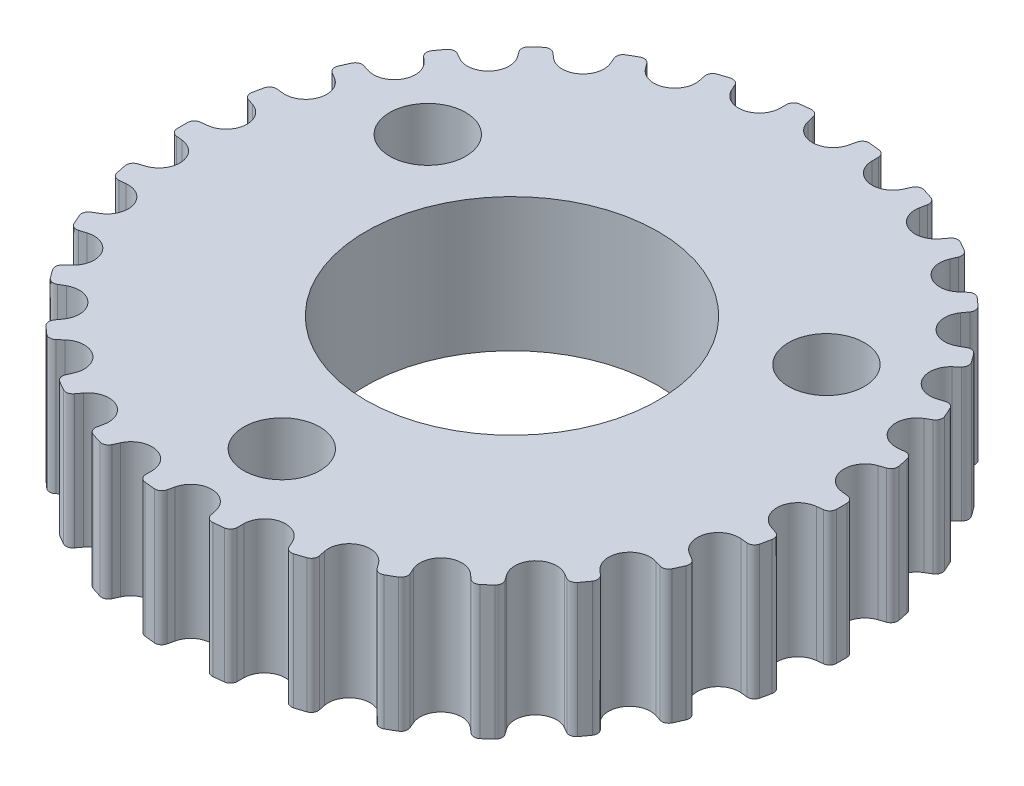
SolidWorks part; units mm, degrees
ref_plane "Front Plane" through (0, 0, 0) normal (0, 0, 1) x (1, 0, 0)
ref_plane "Top Plane" through (0, 0, 0) normal (0, 1, 0) x (1, 0, 0)
ref_plane "Right Plane" through (0, 0, 0) normal (1, 0, 0) x (0, 0, -1)
sketch "Sketch1" plane through (0, 0, 0) normal (0, 1, 0) x (1, 0, 0)
  circle A0 centre (0, 0) radius 14.3239
  dimension "D1" = 28.6479
extrude "Boss-Extrude1" add sketch "Sketch1" along normal blind 5.8
sketch "Sketch2" plane through (0, 5.8, 0) normal (0, 1, 0) x (1, 0, 0)
  line L0 (0, 0) -> (0, 14.3239) construction
  line L1 (-0.8883, 13.7564) -> (-0.95, 14.0339)
  line L2 (-2.9781, 14.0109) -> (-2.9781, 14.3239)
  line L3 (-2.9781, 14.3239) -> (2.9781, 14.3239)
  line L4 (0.8883, 13.7564) -> (0.95, 14.0339)
  line L5 (2.9781, 14.0109) -> (2.9781, 14.3239)
  circle A0 centre (0, 0) radius 14.3239 construction
  arc A1 (0.8883, 13.7564) -> (-0.8883, 13.7564) centre (0, 13.9539) cw
  arc A2 (-0.95, 14.0339) -> (-1.2694, 14.2676) centre (-1.2428, 13.9688) ccw
  arc A4 (0.95, 14.0339) -> (1.2694, 14.2676) centre (1.2428, 13.9688) cw
  arc A5 (-1.2694, 14.2676) -> (-2.9781, 14.0109) centre (0, 0) ccw
  arc A6 (1.2694, 14.2676) -> (2.9781, 14.0109) centre (0, 0) cw
  circle A8 centre (0, 0) radius 14.3239 construction
  point P11 (0, 14.3239)
  point P19 (0, 13.0439)
  dimension "D3" = 0.3
  dimension "D5" = 0.91
  dimension "D2" = 0.95
  dimension "D4" = 1.28
  dimension "D6" = 12
extrude "Cut-Extrude1" cut sketch "Sketch2" against normal through all
pattern_circular "CirPattern1" count 30 over 360 about axis through (0, 5.8, 0) along (0, -1, 0) of "Cut-Extrude1"
sketch "Sketch3" plane through (0, 0, 0) normal (0, -1, 0) x (1, 0, 0)
  circle A0 centre (0, 0) radius 6.35
  dimension "D1" = 12.7
extrude "Cut-Extrude2" cut sketch "Sketch3" against normal through all
sketch "Sketch4" plane through (0, 0, 0) normal (0, -1, 0) x (1, 0, 0)
  line L0 (0, 0) -> (0, 10) construction
  circle A0 centre (0, 10) radius 1.65
  circle A1 centre (8.6603, -5) radius 1.65
  circle A2 centre (-8.6603, -5) radius 1.65
  point P14 (0, 0)
  dimension "D1" = 3.3
  dimension "D2" = 10
  dimension "D3" = 3
extrude "Cut-Extrude3" cut sketch "Sketch4" against normal through all
sketch "Sketch5" plane through (0, 0, 0) normal (0, -1, 0) x (1, 0, 0)
  line L120 (6.3264, -12.2653) -> (6.4956, -12.4937)
  line L121 (7.5721, -11.8722) -> (7.4589, -11.6115)
  line L122 (8.7383, -10.682) -> (8.9513, -10.8702)
  line L123 (9.875, -10.0385) -> (9.7101, -9.807)
  line L124 (10.7682, -8.6318) -> (11.0157, -8.7716)
  line L125 (11.7463, -7.766) -> (11.5369, -7.5738)
  line L126 (12.3276, -6.2043) -> (12.5987, -6.2896)
  line L127 (13.1043, -5.1541) -> (12.8594, -5.0097)
  line L128 (13.3481, -3.5057) -> (13.6311, -3.5327)
  line L129 (13.8895, -2.3169) -> (13.62, -2.2266)
  line L130 (13.7853, -0.6538) -> (14.0677, -0.6215)
  line L131 (14.0677, 0.6215) -> (13.7853, 0.6538)
  line L132 (13.62, 2.2266) -> (13.8895, 2.3169)
  line L133 (13.6311, 3.5327) -> (13.3481, 3.5057)
  line L134 (12.8594, 5.0097) -> (13.1043, 5.1541)
  line L135 (12.5987, 6.2896) -> (12.3276, 6.2043)
  line L136 (11.5369, 7.5738) -> (11.7463, 7.766)
  line L137 (11.0157, 8.7716) -> (10.7682, 8.6318)
  line L138 (9.7101, 9.807) -> (9.875, 10.0385)
  line L139 (8.9513, 10.8702) -> (8.7383, 10.682)
  line L140 (7.4589, 11.6115) -> (7.5721, 11.8722)
  line L141 (6.4956, 12.4937) -> (6.3264, 12.2653)
  line L142 (4.8817, 12.9085) -> (4.9382, 13.1871)
  line L143 (3.7561, 13.5712) -> (3.638, 13.3126)
  line L144 (2.0912, 13.6414) -> (2.0886, 13.9257)
  line L145 (0.8524, 14.0556) -> (0.7907, 13.7781)
  line L146 (-0.7907, 13.7781) -> (-0.8524, 14.0556)
  line L147 (-2.0886, 13.9257) -> (-2.0912, 13.6414)
  line L148 (-3.638, 13.3126) -> (-3.7561, 13.5712)
  line L149 (-4.9382, 13.1871) -> (-4.8817, 12.9085)
  line L150 (-6.3264, 12.2653) -> (-6.4956, 12.4937)
  line L151 (-7.5721, 11.8722) -> (-7.4589, 11.6115)
  line L152 (-8.7383, 10.682) -> (-8.9513, 10.8702)
  line L153 (-9.875, 10.0385) -> (-9.7101, 9.807)
  line L154 (-10.7682, 8.6318) -> (-11.0157, 8.7716)
  line L155 (-11.7463, 7.766) -> (-11.5369, 7.5738)
  line L156 (-12.3276, 6.2043) -> (-12.5987, 6.2896)
  line L157 (-13.1043, 5.1541) -> (-12.8594, 5.0097)
  line L158 (-13.3481, 3.5057) -> (-13.6311, 3.5327)
  line L159 (-13.8895, 2.3169) -> (-13.62, 2.2266)
  line L160 (-13.7853, 0.6538) -> (-14.0677, 0.6215)
  line L161 (-14.0677, -0.6215) -> (-13.7853, -0.6538)
  line L162 (-13.62, -2.2266) -> (-13.8895, -2.3169)
  line L163 (-13.6311, -3.5327) -> (-13.3481, -3.5057)
  line L164 (-12.8594, -5.0097) -> (-13.1043, -5.1541)
  line L165 (-12.5987, -6.2896) -> (-12.3276, -6.2043)
  line L166 (-11.5369, -7.5738) -> (-11.7463, -7.766)
  line L167 (-11.0157, -8.7716) -> (-10.7682, -8.6318)
  line L168 (-9.7101, -9.807) -> (-9.875, -10.0385)
  line L169 (-8.9513, -10.8702) -> (-8.7383, -10.682)
  line L170 (-7.4589, -11.6115) -> (-7.5721, -11.8722)
  line L171 (-6.4956, -12.4937) -> (-6.3264, -12.2653)
  line L172 (-4.8817, -12.9085) -> (-4.9382, -13.1871)
  line L173 (-3.7561, -13.5712) -> (-3.638, -13.3126)
  line L174 (-2.0912, -13.6414) -> (-2.0886, -13.9257)
  line L175 (-0.8524, -14.0556) -> (-0.7907, -13.7781)
  line L176 (0.7907, -13.7781) -> (0.8524, -14.0556)
  line L177 (2.0886, -13.9257) -> (2.0912, -13.6414)
  line L178 (3.638, -13.3126) -> (3.7561, -13.5712)
  line L179 (4.9382, -13.1871) -> (4.8817, -12.9085)
  line L180 (6.3264, -12.2653) -> (6.4956, -12.4937)
  line L181 (7.5721, -11.8722) -> (7.4589, -11.6115)
  line L182 (8.7383, -10.682) -> (8.9513, -10.8702)
  line L183 (9.875, -10.0385) -> (9.7101, -9.807)
  line L184 (10.7682, -8.6318) -> (11.0157, -8.7716)
  line L185 (11.7463, -7.766) -> (11.5369, -7.5738)
  line L186 (12.3276, -6.2043) -> (12.5987, -6.2896)
  line L187 (13.1043, -5.1541) -> (12.8594, -5.0097)
  line L188 (13.3481, -3.5057) -> (13.6311, -3.5327)
  line L189 (13.8895, -2.3169) -> (13.62, -2.2266)
  line L190 (13.7853, -0.6538) -> (14.0677, -0.6215)
  line L191 (14.0677, 0.6215) -> (13.7853, 0.6538)
  line L192 (13.62, 2.2266) -> (13.8895, 2.3169)
  line L193 (13.6311, 3.5327) -> (13.3481, 3.5057)
  line L194 (12.8594, 5.0097) -> (13.1043, 5.1541)
  line L195 (12.5987, 6.2896) -> (12.3276, 6.2043)
  line L196 (11.5369, 7.5738) -> (11.7463, 7.766)
  line L197 (11.0157, 8.7716) -> (10.7682, 8.6318)
  line L198 (9.7101, 9.807) -> (9.875, 10.0385)
  line L199 (8.9513, 10.8702) -> (8.7383, 10.682)
  line L200 (7.4589, 11.6115) -> (7.5721, 11.8722)
  line L201 (6.4956, 12.4937) -> (6.3264, 12.2653)
  line L202 (4.8817, 12.9085) -> (4.9382, 13.1871)
  line L203 (3.7561, 13.5712) -> (3.638, 13.3126)
  line L204 (2.0912, 13.6414) -> (2.0886, 13.9257)
  line L205 (0.8524, 14.0556) -> (0.7907, 13.7781)
  line L206 (-0.7907, 13.7781) -> (-0.8524, 14.0556)
  line L207 (-2.0886, 13.9257) -> (-2.0912, 13.6414)
  line L208 (-3.638, 13.3126) -> (-3.7561, 13.5712)
  line L209 (-4.9382, 13.1871) -> (-4.8817, 12.9085)
  line L210 (-6.3264, 12.2653) -> (-6.4956, 12.4937)
  line L211 (-7.5721, 11.8722) -> (-7.4589, 11.6115)
  line L212 (-8.7383, 10.682) -> (-8.9513, 10.8702)
  line L213 (-9.875, 10.0385) -> (-9.7101, 9.807)
  line L214 (-10.7682, 8.6318) -> (-11.0157, 8.7716)
  line L215 (-11.7463, 7.766) -> (-11.5369, 7.5738)
  line L216 (-12.3276, 6.2043) -> (-12.5987, 6.2896)
  line L217 (-13.1043, 5.1541) -> (-12.8594, 5.0097)
  line L218 (-13.3481, 3.5057) -> (-13.6311, 3.5327)
  line L219 (-13.8895, 2.3169) -> (-13.62, 2.2266)
  line L220 (-13.7853, 0.6538) -> (-14.0677, 0.6215)
  line L221 (-14.0677, -0.6215) -> (-13.7853, -0.6538)
  line L222 (-13.62, -2.2266) -> (-13.8895, -2.3169)
  line L223 (-13.6311, -3.5327) -> (-13.3481, -3.5057)
  line L224 (-12.8594, -5.0097) -> (-13.1043, -5.1541)
  line L225 (-12.5987, -6.2896) -> (-12.3276, -6.2043)
  line L226 (-11.5369, -7.5738) -> (-11.7463, -7.766)
  line L227 (-11.0157, -8.7716) -> (-10.7682, -8.6318)
  line L228 (-9.7101, -9.807) -> (-9.875, -10.0385)
  line L229 (-8.9513, -10.8702) -> (-8.7383, -10.682)
  line L230 (-7.4589, -11.6115) -> (-7.5721, -11.8722)
  line L231 (-6.4956, -12.4937) -> (-6.3264, -12.2653)
  line L232 (-4.8817, -12.9085) -> (-4.9382, -13.1871)
  line L233 (-3.7561, -13.5712) -> (-3.638, -13.3126)
  line L234 (-2.0912, -13.6414) -> (-2.0886, -13.9257)
  line L235 (-0.8524, -14.0556) -> (-0.7907, -13.7781)
  line L236 (0.7907, -13.7781) -> (0.8524, -14.0556)
  line L237 (2.0886, -13.9257) -> (2.0912, -13.6414)
  line L238 (3.638, -13.3126) -> (3.7561, -13.5712)
  line L239 (4.9382, -13.1871) -> (4.8817, -12.9085)
  circle A120 centre (0, 0) radius 13.0439
  arc A121 (-0.8883, 13.7564) -> (0.8883, 13.7564) centre (0, 13.9539) ccw construction
  arc A240 (6.4956, -12.4937) -> (7.0114, -12.6052) centre (6.817, -12.2556) ccw
  arc A241 (7.0114, -12.6052) -> (7.4107, -12.3747) centre (0, 0) ccw
  arc A242 (7.4107, -12.3747) -> (7.5721, -11.8722) centre (7.2051, -12.0315) ccw
  arc A243 (8.7383, -10.682) -> (7.4589, -11.6115) centre (8.2019, -11.289) ccw
  arc A244 (8.9513, -10.8702) -> (9.479, -10.8719) centre (9.2161, -10.5704) ccw
  arc A245 (9.479, -10.8719) -> (9.8216, -10.5635) centre (0, 0) ccw
  arc A246 (9.8216, -10.5635) -> (9.875, -10.0385) centre (9.5492, -10.2705) ccw
  arc A247 (10.7682, -8.6318) -> (9.7101, -9.807) centre (10.3698, -9.337) ccw
  arc A248 (11.0157, -8.7716) -> (11.5323, -8.6636) centre (11.2124, -8.4233) ccw
  arc A249 (11.5323, -8.6636) -> (11.8032, -8.2906) centre (0, 0) ccw
  arc A250 (11.8032, -8.2906) -> (11.7463, -7.766) centre (11.4759, -8.0607) ccw
  arc A251 (12.3276, -6.2043) -> (11.5369, -7.5738) centre (12.0845, -6.977) ccw
  arc A252 (12.5987, -6.2896) -> (13.0815, -6.0766) centre (12.7187, -5.908) ccw
  arc A253 (13.0815, -6.0766) -> (13.269, -5.6554) centre (0, 0) ccw
  arc A254 (13.269, -5.6554) -> (13.1043, -5.1541) centre (12.901, -5.4986) ccw
  arc A255 (13.3481, -3.5057) -> (12.8594, -5.0097) centre (13.271, -4.312) ccw
  arc A256 (13.6311, -3.5327) -> (14.059, -3.224) centre (13.6691, -3.1346) ccw
  arc A257 (14.059, -3.224) -> (14.1549, -2.7731) centre (0, 0) ccw
  arc A258 (14.1549, -2.7731) -> (13.8895, -2.3169) centre (13.7623, -2.6962) ccw
  arc A259 (13.7853, -0.6538) -> (13.62, -2.2266) centre (13.8775, -1.4586) ccw
  arc A260 (14.0677, -0.6215) -> (14.4221, -0.2305) centre (14.0222, -0.2241) ccw
  arc A261 (14.4221, -0.2305) -> (14.4221, 0.2305) centre (0, 0) ccw
  arc A262 (14.4221, 0.2305) -> (14.0677, 0.6215) centre (14.0222, 0.2241) ccw
  arc A263 (13.62, 2.2266) -> (13.7853, 0.6538) centre (13.8775, 1.4586) ccw
  arc A264 (13.8895, 2.3169) -> (14.1549, 2.7731) centre (13.7623, 2.6962) ccw
  arc A265 (14.1549, 2.7731) -> (14.059, 3.224) centre (0, 0) ccw
  arc A266 (14.059, 3.224) -> (13.6311, 3.5327) centre (13.6691, 3.1346) ccw
  arc A267 (12.8594, 5.0097) -> (13.3481, 3.5057) centre (13.271, 4.312) ccw
  arc A268 (13.1043, 5.1541) -> (13.269, 5.6554) centre (12.901, 5.4986) ccw
  arc A269 (13.269, 5.6554) -> (13.0815, 6.0766) centre (0, 0) ccw
  arc A270 (13.0815, 6.0766) -> (12.5987, 6.2896) centre (12.7187, 5.908) ccw
  arc A271 (11.5369, 7.5738) -> (12.3276, 6.2043) centre (12.0845, 6.977) ccw
  arc A272 (11.7463, 7.766) -> (11.8032, 8.2906) centre (11.4759, 8.0607) ccw
  arc A273 (11.8032, 8.2906) -> (11.5323, 8.6636) centre (0, 0) ccw
  arc A274 (11.5323, 8.6636) -> (11.0157, 8.7716) centre (11.2124, 8.4233) ccw
  arc A275 (9.7101, 9.807) -> (10.7682, 8.6318) centre (10.3698, 9.337) ccw
  arc A276 (9.875, 10.0385) -> (9.8216, 10.5635) centre (9.5492, 10.2705) ccw
  arc A277 (9.8216, 10.5635) -> (9.479, 10.8719) centre (0, 0) ccw
  arc A278 (9.479, 10.8719) -> (8.9513, 10.8702) centre (9.2161, 10.5704) ccw
  arc A279 (7.4589, 11.6115) -> (8.7383, 10.682) centre (8.2019, 11.289) ccw
  arc A280 (7.5721, 11.8722) -> (7.4107, 12.3747) centre (7.2051, 12.0315) ccw
  arc A281 (7.4107, 12.3747) -> (7.0114, 12.6052) centre (0, 0) ccw
  arc A282 (7.0114, 12.6052) -> (6.4956, 12.4937) centre (6.817, 12.2556) ccw
  arc A283 (4.8817, 12.9085) -> (6.3264, 12.2653) centre (5.6756, 12.7476) ccw
  arc A284 (4.9382, 13.1871) -> (4.6759, 13.645) centre (4.5462, 13.2666) ccw
  arc A285 (4.6759, 13.645) -> (4.2375, 13.7875) centre (0, 0) ccw
  arc A286 (4.2375, 13.7875) -> (3.7561, 13.5712) centre (4.12, 13.4051) ccw
  arc A287 (2.0912, 13.6414) -> (3.638, 13.3126) centre (2.9012, 13.649) ccw
  arc A288 (2.0886, 13.9257) -> (1.7367, 14.319) centre (1.6886, 13.9219) ccw
  arc A289 (1.7367, 14.319) -> (1.2783, 14.3672) centre (0, 0) ccw
  arc A290 (1.2783, 14.3672) -> (0.8524, 14.0556) centre (1.2428, 13.9688) ccw
  arc A291 (-0.7907, 13.7781) -> (0.7907, 13.7781) centre (0, 13.9539) ccw
  arc A292 (-0.8524, 14.0556) -> (-1.2783, 14.3672) centre (-1.2428, 13.9688) ccw
  arc A293 (-1.2783, 14.3672) -> (-1.7367, 14.319) centre (0, 0) ccw
  arc A294 (-1.7367, 14.319) -> (-2.0886, 13.9257) centre (-1.6886, 13.9219) ccw
  arc A295 (-3.638, 13.3126) -> (-2.0912, 13.6414) centre (-2.9012, 13.649) ccw
  arc A296 (-3.7561, 13.5712) -> (-4.2375, 13.7875) centre (-4.12, 13.4051) ccw
  arc A297 (-4.2375, 13.7875) -> (-4.6759, 13.645) centre (0, 0) ccw
  arc A298 (-4.6759, 13.645) -> (-4.9382, 13.1871) centre (-4.5462, 13.2666) ccw
  arc A299 (-6.3264, 12.2653) -> (-4.8817, 12.9085) centre (-5.6756, 12.7476) ccw
  arc A300 (-6.4956, 12.4937) -> (-7.0114, 12.6052) centre (-6.817, 12.2556) ccw
  arc A301 (-7.0114, 12.6052) -> (-7.4107, 12.3747) centre (0, 0) ccw
  arc A302 (-7.4107, 12.3747) -> (-7.5721, 11.8722) centre (-7.2051, 12.0315) ccw
  arc A303 (-8.7383, 10.682) -> (-7.4589, 11.6115) centre (-8.2019, 11.289) ccw
  arc A304 (-8.9513, 10.8702) -> (-9.479, 10.8719) centre (-9.2161, 10.5704) ccw
  arc A305 (-9.479, 10.8719) -> (-9.8216, 10.5635) centre (0, 0) ccw
  arc A306 (-9.8216, 10.5635) -> (-9.875, 10.0385) centre (-9.5492, 10.2705) ccw
  arc A307 (-10.7682, 8.6318) -> (-9.7101, 9.807) centre (-10.3698, 9.337) ccw
  arc A308 (-11.0157, 8.7716) -> (-11.5323, 8.6636) centre (-11.2124, 8.4233) ccw
  arc A309 (-11.5323, 8.6636) -> (-11.8032, 8.2906) centre (0, 0) ccw
  arc A310 (-11.8032, 8.2906) -> (-11.7463, 7.766) centre (-11.4759, 8.0607) ccw
  arc A311 (-12.3276, 6.2043) -> (-11.5369, 7.5738) centre (-12.0845, 6.977) ccw
  arc A312 (-12.5987, 6.2896) -> (-13.0815, 6.0766) centre (-12.7187, 5.908) ccw
  arc A313 (-13.0815, 6.0766) -> (-13.269, 5.6554) centre (0, 0) ccw
  arc A314 (-13.269, 5.6554) -> (-13.1043, 5.1541) centre (-12.901, 5.4986) ccw
  arc A315 (-13.3481, 3.5057) -> (-12.8594, 5.0097) centre (-13.271, 4.312) ccw
  arc A316 (-13.6311, 3.5327) -> (-14.059, 3.224) centre (-13.6691, 3.1346) ccw
  arc A317 (-14.059, 3.224) -> (-14.1549, 2.7731) centre (0, 0) ccw
  arc A318 (-14.1549, 2.7731) -> (-13.8895, 2.3169) centre (-13.7623, 2.6962) ccw
  arc A319 (-13.7853, 0.6538) -> (-13.62, 2.2266) centre (-13.8775, 1.4586) ccw
  arc A320 (-14.0677, 0.6215) -> (-14.4221, 0.2305) centre (-14.0222, 0.2241) ccw
  arc A321 (-14.4221, 0.2305) -> (-14.4221, -0.2305) centre (0, 0) ccw
  arc A322 (-14.4221, -0.2305) -> (-14.0677, -0.6215) centre (-14.0222, -0.2241) ccw
  arc A323 (-13.62, -2.2266) -> (-13.7853, -0.6538) centre (-13.8775, -1.4586) ccw
  arc A324 (-13.8895, -2.3169) -> (-14.1549, -2.7731) centre (-13.7623, -2.6962) ccw
  arc A325 (-14.1549, -2.7731) -> (-14.059, -3.224) centre (0, 0) ccw
  arc A326 (-14.059, -3.224) -> (-13.6311, -3.5327) centre (-13.6691, -3.1346) ccw
  arc A327 (-12.8594, -5.0097) -> (-13.3481, -3.5057) centre (-13.271, -4.312) ccw
  arc A328 (-13.1043, -5.1541) -> (-13.269, -5.6554) centre (-12.901, -5.4986) ccw
  arc A329 (-13.269, -5.6554) -> (-13.0815, -6.0766) centre (0, 0) ccw
  arc A330 (-13.0815, -6.0766) -> (-12.5987, -6.2896) centre (-12.7187, -5.908) ccw
  arc A331 (-11.5369, -7.5738) -> (-12.3276, -6.2043) centre (-12.0845, -6.977) ccw
  arc A332 (-11.7463, -7.766) -> (-11.8032, -8.2906) centre (-11.4759, -8.0607) ccw
  arc A333 (-11.8032, -8.2906) -> (-11.5323, -8.6636) centre (0, 0) ccw
  arc A334 (-11.5323, -8.6636) -> (-11.0157, -8.7716) centre (-11.2124, -8.4233) ccw
  arc A335 (-9.7101, -9.807) -> (-10.7682, -8.6318) centre (-10.3698, -9.337) ccw
  arc A336 (-9.875, -10.0385) -> (-9.8216, -10.5635) centre (-9.5492, -10.2705) ccw
  arc A337 (-9.8216, -10.5635) -> (-9.479, -10.8719) centre (0, 0) ccw
  arc A338 (-9.479, -10.8719) -> (-8.9513, -10.8702) centre (-9.2161, -10.5704) ccw
  arc A339 (-7.4589, -11.6115) -> (-8.7383, -10.682) centre (-8.2019, -11.289) ccw
  arc A340 (-7.5721, -11.8722) -> (-7.4107, -12.3747) centre (-7.2051, -12.0315) ccw
  arc A341 (-7.4107, -12.3747) -> (-7.0114, -12.6052) centre (0, 0) ccw
  arc A342 (-7.0114, -12.6052) -> (-6.4956, -12.4937) centre (-6.817, -12.2556) ccw
  arc A343 (-4.8817, -12.9085) -> (-6.3264, -12.2653) centre (-5.6756, -12.7476) ccw
  arc A344 (-4.9382, -13.1871) -> (-4.6759, -13.645) centre (-4.5462, -13.2666) ccw
  arc A345 (-4.6759, -13.645) -> (-4.2375, -13.7875) centre (0, 0) ccw
  arc A346 (-4.2375, -13.7875) -> (-3.7561, -13.5712) centre (-4.12, -13.4051) ccw
  arc A347 (-2.0912, -13.6414) -> (-3.638, -13.3126) centre (-2.9012, -13.649) ccw
  arc A348 (-2.0886, -13.9257) -> (-1.7367, -14.319) centre (-1.6886, -13.9219) ccw
  arc A349 (-1.7367, -14.319) -> (-1.2783, -14.3672) centre (0, 0) ccw
  arc A350 (-1.2783, -14.3672) -> (-0.8524, -14.0556) centre (-1.2428, -13.9688) ccw
  arc A351 (0.7907, -13.7781) -> (-0.7907, -13.7781) centre (0, -13.9539) ccw
  arc A352 (0.8524, -14.0556) -> (1.2783, -14.3672) centre (1.2428, -13.9688) ccw
  arc A353 (1.2783, -14.3672) -> (1.7367, -14.319) centre (0, 0) ccw
  arc A354 (1.7367, -14.319) -> (2.0886, -13.9257) centre (1.6886, -13.9219) ccw
  arc A355 (3.638, -13.3126) -> (2.0912, -13.6414) centre (2.9012, -13.649) ccw
  arc A356 (3.7561, -13.5712) -> (4.2375, -13.7875) centre (4.12, -13.4051) ccw
  arc A357 (4.2375, -13.7875) -> (4.6759, -13.645) centre (0, 0) ccw
  arc A358 (4.6759, -13.645) -> (4.9382, -13.1871) centre (4.5462, -13.2666) ccw
  arc A359 (6.3264, -12.2653) -> (4.8817, -12.9085) centre (5.6756, -12.7476) ccw
  arc A360 (6.4956, -12.4937) -> (7.0114, -12.6052) centre (6.817, -12.2556) ccw
  arc A361 (7.0114, -12.6052) -> (7.4107, -12.3747) centre (0, 0) ccw
  arc A362 (7.4107, -12.3747) -> (7.5721, -11.8722) centre (7.2051, -12.0315) ccw
  arc A363 (8.7383, -10.682) -> (7.4589, -11.6115) centre (8.2019, -11.289) ccw
  arc A364 (8.9513, -10.8702) -> (9.479, -10.8719) centre (9.2161, -10.5704) ccw
  arc A365 (9.479, -10.8719) -> (9.8216, -10.5635) centre (0, 0) ccw
  arc A366 (9.8216, -10.5635) -> (9.875, -10.0385) centre (9.5492, -10.2705) ccw
  arc A367 (10.7682, -8.6318) -> (9.7101, -9.807) centre (10.3698, -9.337) ccw
  arc A368 (11.0157, -8.7716) -> (11.5323, -8.6636) centre (11.2124, -8.4233) ccw
  arc A369 (11.5323, -8.6636) -> (11.8032, -8.2906) centre (0, 0) ccw
  arc A370 (11.8032, -8.2906) -> (11.7463, -7.766) centre (11.4759, -8.0607) ccw
  arc A371 (12.3276, -6.2043) -> (11.5369, -7.5738) centre (12.0845, -6.977) ccw
  arc A372 (12.5987, -6.2896) -> (13.0815, -6.0766) centre (12.7187, -5.908) ccw
  arc A373 (13.0815, -6.0766) -> (13.269, -5.6554) centre (0, 0) ccw
  arc A374 (13.269, -5.6554) -> (13.1043, -5.1541) centre (12.901, -5.4986) ccw
  arc A375 (13.3481, -3.5057) -> (12.8594, -5.0097) centre (13.271, -4.312) ccw
  arc A376 (13.6311, -3.5327) -> (14.059, -3.224) centre (13.6691, -3.1346) ccw
  arc A377 (14.059, -3.224) -> (14.1549, -2.7731) centre (0, 0) ccw
  arc A378 (14.1549, -2.7731) -> (13.8895, -2.3169) centre (13.7623, -2.6962) ccw
  arc A379 (13.7853, -0.6538) -> (13.62, -2.2266) centre (13.8775, -1.4586) ccw
  arc A380 (14.0677, -0.6215) -> (14.4221, -0.2305) centre (14.0222, -0.2241) ccw
  arc A381 (14.4221, -0.2305) -> (14.4221, 0.2305) centre (0, 0) ccw
  arc A382 (14.4221, 0.2305) -> (14.0677, 0.6215) centre (14.0222, 0.2241) ccw
  arc A383 (13.62, 2.2266) -> (13.7853, 0.6538) centre (13.8775, 1.4586) ccw
  arc A384 (13.8895, 2.3169) -> (14.1549, 2.7731) centre (13.7623, 2.6962) ccw
  arc A385 (14.1549, 2.7731) -> (14.059, 3.224) centre (0, 0) ccw
  arc A386 (14.059, 3.224) -> (13.6311, 3.5327) centre (13.6691, 3.1346) ccw
  arc A387 (12.8594, 5.0097) -> (13.3481, 3.5057) centre (13.271, 4.312) ccw
  arc A388 (13.1043, 5.1541) -> (13.269, 5.6554) centre (12.901, 5.4986) ccw
  arc A389 (13.269, 5.6554) -> (13.0815, 6.0766) centre (0, 0) ccw
  arc A390 (13.0815, 6.0766) -> (12.5987, 6.2896) centre (12.7187, 5.908) ccw
  arc A391 (11.5369, 7.5738) -> (12.3276, 6.2043) centre (12.0845, 6.977) ccw
  arc A392 (11.7463, 7.766) -> (11.8032, 8.2906) centre (11.4759, 8.0607) ccw
  arc A393 (11.8032, 8.2906) -> (11.5323, 8.6636) centre (0, 0) ccw
  arc A394 (11.5323, 8.6636) -> (11.0157, 8.7716) centre (11.2124, 8.4233) ccw
  arc A395 (9.7101, 9.807) -> (10.7682, 8.6318) centre (10.3698, 9.337) ccw
  arc A396 (9.875, 10.0385) -> (9.8216, 10.5635) centre (9.5492, 10.2705) ccw
  arc A397 (9.8216, 10.5635) -> (9.479, 10.8719) centre (0, 0) ccw
  arc A398 (9.479, 10.8719) -> (8.9513, 10.8702) centre (9.2161, 10.5704) ccw
  arc A399 (7.4589, 11.6115) -> (8.7383, 10.682) centre (8.2019, 11.289) ccw
  arc A400 (7.5721, 11.8722) -> (7.4107, 12.3747) centre (7.2051, 12.0315) ccw
  arc A401 (7.4107, 12.3747) -> (7.0114, 12.6052) centre (0, 0) ccw
  arc A402 (7.0114, 12.6052) -> (6.4956, 12.4937) centre (6.817, 12.2556) ccw
  arc A403 (4.8817, 12.9085) -> (6.3264, 12.2653) centre (5.6756, 12.7476) ccw
  arc A404 (4.9382, 13.1871) -> (4.6759, 13.645) centre (4.5462, 13.2666) ccw
  arc A405 (4.6759, 13.645) -> (4.2375, 13.7875) centre (0, 0) ccw
  arc A406 (4.2375, 13.7875) -> (3.7561, 13.5712) centre (4.12, 13.4051) ccw
  arc A407 (2.0912, 13.6414) -> (3.638, 13.3126) centre (2.9012, 13.649) ccw
  arc A408 (2.0886, 13.9257) -> (1.7367, 14.319) centre (1.6886, 13.9219) ccw
  arc A409 (1.7367, 14.319) -> (1.2783, 14.3672) centre (0, 0) ccw
  arc A410 (1.2783, 14.3672) -> (0.8524, 14.0556) centre (1.2428, 13.9688) ccw
  arc A411 (-0.7907, 13.7781) -> (0.7907, 13.7781) centre (0, 13.9539) ccw
  arc A412 (-0.8524, 14.0556) -> (-1.2783, 14.3672) centre (-1.2428, 13.9688) ccw
  arc A413 (-1.2783, 14.3672) -> (-1.7367, 14.319) centre (0, 0) ccw
  arc A414 (-1.7367, 14.319) -> (-2.0886, 13.9257) centre (-1.6886, 13.9219) ccw
  arc A415 (-3.638, 13.3126) -> (-2.0912, 13.6414) centre (-2.9012, 13.649) ccw
  arc A416 (-3.7561, 13.5712) -> (-4.2375, 13.7875) centre (-4.12, 13.4051) ccw
  arc A417 (-4.2375, 13.7875) -> (-4.6759, 13.645) centre (0, 0) ccw
  arc A418 (-4.6759, 13.645) -> (-4.9382, 13.1871) centre (-4.5462, 13.2666) ccw
  arc A419 (-6.3264, 12.2653) -> (-4.8817, 12.9085) centre (-5.6756, 12.7476) ccw
  arc A420 (-6.4956, 12.4937) -> (-7.0114, 12.6052) centre (-6.817, 12.2556) ccw
  arc A421 (-7.0114, 12.6052) -> (-7.4107, 12.3747) centre (0, 0) ccw
  arc A422 (-7.4107, 12.3747) -> (-7.5721, 11.8722) centre (-7.2051, 12.0315) ccw
  arc A423 (-8.7383, 10.682) -> (-7.4589, 11.6115) centre (-8.2019, 11.289) ccw
  arc A424 (-8.9513, 10.8702) -> (-9.479, 10.8719) centre (-9.2161, 10.5704) ccw
  arc A425 (-9.479, 10.8719) -> (-9.8216, 10.5635) centre (0, 0) ccw
  arc A426 (-9.8216, 10.5635) -> (-9.875, 10.0385) centre (-9.5492, 10.2705) ccw
  arc A427 (-10.7682, 8.6318) -> (-9.7101, 9.807) centre (-10.3698, 9.337) ccw
  arc A428 (-11.0157, 8.7716) -> (-11.5323, 8.6636) centre (-11.2124, 8.4233) ccw
  arc A429 (-11.5323, 8.6636) -> (-11.8032, 8.2906) centre (0, 0) ccw
  arc A430 (-11.8032, 8.2906) -> (-11.7463, 7.766) centre (-11.4759, 8.0607) ccw
  arc A431 (-12.3276, 6.2043) -> (-11.5369, 7.5738) centre (-12.0845, 6.977) ccw
  arc A432 (-12.5987, 6.2896) -> (-13.0815, 6.0766) centre (-12.7187, 5.908) ccw
  arc A433 (-13.0815, 6.0766) -> (-13.269, 5.6554) centre (0, 0) ccw
  arc A434 (-13.269, 5.6554) -> (-13.1043, 5.1541) centre (-12.901, 5.4986) ccw
  arc A435 (-13.3481, 3.5057) -> (-12.8594, 5.0097) centre (-13.271, 4.312) ccw
  arc A436 (-13.6311, 3.5327) -> (-14.059, 3.224) centre (-13.6691, 3.1346) ccw
  arc A437 (-14.059, 3.224) -> (-14.1549, 2.7731) centre (0, 0) ccw
  arc A438 (-14.1549, 2.7731) -> (-13.8895, 2.3169) centre (-13.7623, 2.6962) ccw
  arc A439 (-13.7853, 0.6538) -> (-13.62, 2.2266) centre (-13.8775, 1.4586) ccw
  arc A440 (-14.0677, 0.6215) -> (-14.4221, 0.2305) centre (-14.0222, 0.2241) ccw
  arc A441 (-14.4221, 0.2305) -> (-14.4221, -0.2305) centre (0, 0) ccw
  arc A442 (-14.4221, -0.2305) -> (-14.0677, -0.6215) centre (-14.0222, -0.2241) ccw
  arc A443 (-13.62, -2.2266) -> (-13.7853, -0.6538) centre (-13.8775, -1.4586) ccw
  arc A444 (-13.8895, -2.3169) -> (-14.1549, -2.7731) centre (-13.7623, -2.6962) ccw
  arc A445 (-14.1549, -2.7731) -> (-14.059, -3.224) centre (0, 0) ccw
  arc A446 (-14.059, -3.224) -> (-13.6311, -3.5327) centre (-13.6691, -3.1346) ccw
  arc A447 (-12.8594, -5.0097) -> (-13.3481, -3.5057) centre (-13.271, -4.312) ccw
  arc A448 (-13.1043, -5.1541) -> (-13.269, -5.6554) centre (-12.901, -5.4986) ccw
  arc A449 (-13.269, -5.6554) -> (-13.0815, -6.0766) centre (0, 0) ccw
  arc A450 (-13.0815, -6.0766) -> (-12.5987, -6.2896) centre (-12.7187, -5.908) ccw
  arc A451 (-11.5369, -7.5738) -> (-12.3276, -6.2043) centre (-12.0845, -6.977) ccw
  arc A452 (-11.7463, -7.766) -> (-11.8032, -8.2906) centre (-11.4759, -8.0607) ccw
  arc A453 (-11.8032, -8.2906) -> (-11.5323, -8.6636) centre (0, 0) ccw
  arc A454 (-11.5323, -8.6636) -> (-11.0157, -8.7716) centre (-11.2124, -8.4233) ccw
  arc A455 (-9.7101, -9.807) -> (-10.7682, -8.6318) centre (-10.3698, -9.337) ccw
  arc A456 (-9.875, -10.0385) -> (-9.8216, -10.5635) centre (-9.5492, -10.2705) ccw
  arc A457 (-9.8216, -10.5635) -> (-9.479, -10.8719) centre (0, 0) ccw
  arc A458 (-9.479, -10.8719) -> (-8.9513, -10.8702) centre (-9.2161, -10.5704) ccw
  arc A459 (-7.4589, -11.6115) -> (-8.7383, -10.682) centre (-8.2019, -11.289) ccw
  arc A460 (-7.5721, -11.8722) -> (-7.4107, -12.3747) centre (-7.2051, -12.0315) ccw
  arc A461 (-7.4107, -12.3747) -> (-7.0114, -12.6052) centre (0, 0) ccw
  arc A462 (-7.0114, -12.6052) -> (-6.4956, -12.4937) centre (-6.817, -12.2556) ccw
  arc A463 (-4.8817, -12.9085) -> (-6.3264, -12.2653) centre (-5.6756, -12.7476) ccw
  arc A464 (-4.9382, -13.1871) -> (-4.6759, -13.645) centre (-4.5462, -13.2666) ccw
  arc A465 (-4.6759, -13.645) -> (-4.2375, -13.7875) centre (0, 0) ccw
  arc A466 (-4.2375, -13.7875) -> (-3.7561, -13.5712) centre (-4.12, -13.4051) ccw
  arc A467 (-2.0912, -13.6414) -> (-3.638, -13.3126) centre (-2.9012, -13.649) ccw
  arc A468 (-2.0886, -13.9257) -> (-1.7367, -14.319) centre (-1.6886, -13.9219) ccw
  arc A469 (-1.7367, -14.319) -> (-1.2783, -14.3672) centre (0, 0) ccw
  arc A470 (-1.2783, -14.3672) -> (-0.8524, -14.0556) centre (-1.2428, -13.9688) ccw
  arc A471 (0.7907, -13.7781) -> (-0.7907, -13.7781) centre (0, -13.9539) ccw
  arc A472 (0.8524, -14.0556) -> (1.2783, -14.3672) centre (1.2428, -13.9688) ccw
  arc A473 (1.2783, -14.3672) -> (1.7367, -14.319) centre (0, 0) ccw
  arc A474 (1.7367, -14.319) -> (2.0886, -13.9257) centre (1.6886, -13.9219) ccw
  arc A475 (3.638, -13.3126) -> (2.0912, -13.6414) centre (2.9012, -13.649) ccw
  arc A476 (3.7561, -13.5712) -> (4.2375, -13.7875) centre (4.12, -13.4051) ccw
  arc A477 (4.2375, -13.7875) -> (4.6759, -13.645) centre (0, 0) ccw
  arc A478 (4.6759, -13.645) -> (4.9382, -13.1871) centre (4.5462, -13.2666) ccw
  arc A479 (6.3264, -12.2653) -> (4.8817, -12.9085) centre (5.6756, -12.7476) ccw
  dimension "D1" = 0.1
extrude "Boss-Extrude2" [suppressed] add sketch "Sketch5" against normal up to surface (5.8 mm away) up to face at (8.6603, 5.8, -6.65)
equation "\"smallPulleyTeeth\"= 15"
equation "\"largePulleyTeeth\"= 30"
equation "\"eighthThick\"= 2.9mm"
equation "\"D1@Sketch1\"=3*\"largePulleyTeeth\"/pi"
equation "\"D1@Boss-Extrude1\" = \"eighthThick\" * 2"
equation "\"D6@Sketch2\"=360/\"largePulleyTeeth\""
equation "\"quarterThick\"=5.9mm"
equation "\"D1@CirPattern1\"=\"largePulleyTeeth\""
equation "\"sixteenthThick\" = 1.7mm"
equation "\"OD\" = 145mm"
equation "\"puckAngle\" = 60.5deg"
equation "\"puckDiam\" = 76.5mm"
equation "\"axlePress\" = 5.9mm"
equation "\"press\" = 0.2mm"
equation "\"wheelClear\" = 0.3mm"
equation "\"10-32clear\" = 4.5mm"
equation "\"D1@Sketch4\"=\"6-32clear\""
equation "\"6-32clear\" = 3.3mm"
equation "\"8-32clear\" = 4.0mm"
